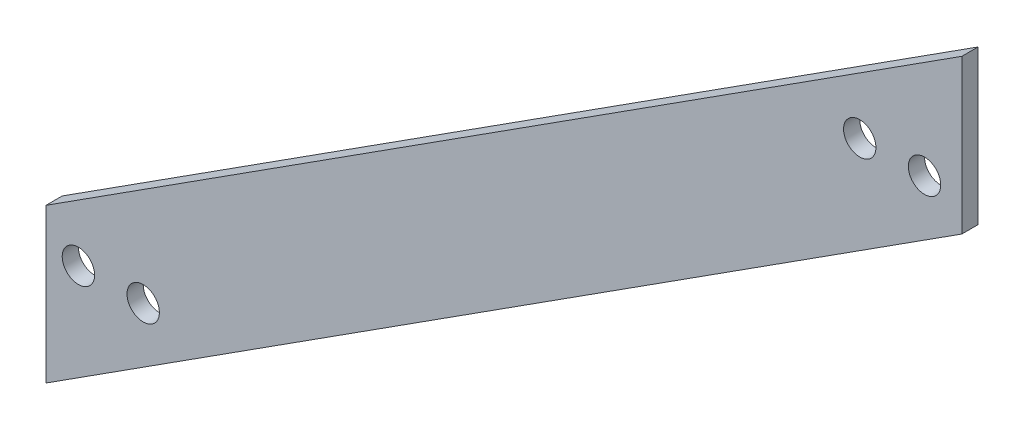
SolidWorks part; units mm, degrees
ref_plane "Front Plane" through (0, 0, 0) normal (0, 0, 1) x (1, 0, 0)
ref_plane "Top Plane" through (0, 0, 0) normal (0, 1, 0) x (1, 0, 0)
ref_plane "Right Plane" through (0, 0, 0) normal (1, 0, 0) x (0, 0, -1)
sketch "Sketch1" plane through (0, 0, 0) normal (0, 0, 1) x (1, 0, 0)
  line L0 (0, 0) -> (0, -45.2527)
  line L1 (0, -45.2527) -> (269.24, 127.2955)
  line L2 (269.24, 127.2955) -> (269.24, 172.5483)
  line L4 (269.24, 172.5483) -> (0, 0)
  line L6 (269.24, 172.5483) -> (289.7978, 140.4704) construction
  line L7 (289.7978, 140.4704) -> (269.24, 127.2955) construction
  line L8 (0, 0) -> (-20.5578, -13.1749) construction
  line L9 (-20.5578, -13.1749) -> (0, -45.2527) construction
  circle A0 centre (9.525, -10.6518) radius 4.7625
  circle A1 centre (28.575, -10.6518) radius 4.7625
  circle A2 centre (239.2348, 136.6682) radius 4.7625
  circle A3 centre (258.2848, 136.6682) radius 4.7625
  dimension "D5" = 9.525
  dimension "D9" = 9.525
  dimension "D1" = 38.1
  dimension "D2" = 147.32
  dimension "D3" = 269.24
  dimension "D4" = 319.786
  dimension "D6" = 301.4751
  dimension "D7" = 317.514
  dimension "D8" = 28.5836
  dimension "D10" = 44.6225
  dimension "D11" = 13.8023
  dimension "D12" = 344.2032
  dimension "D13" = 24.0812
extrude "Boss-Extrude1" add sketch "Sketch1" along normal blind 4.7625
